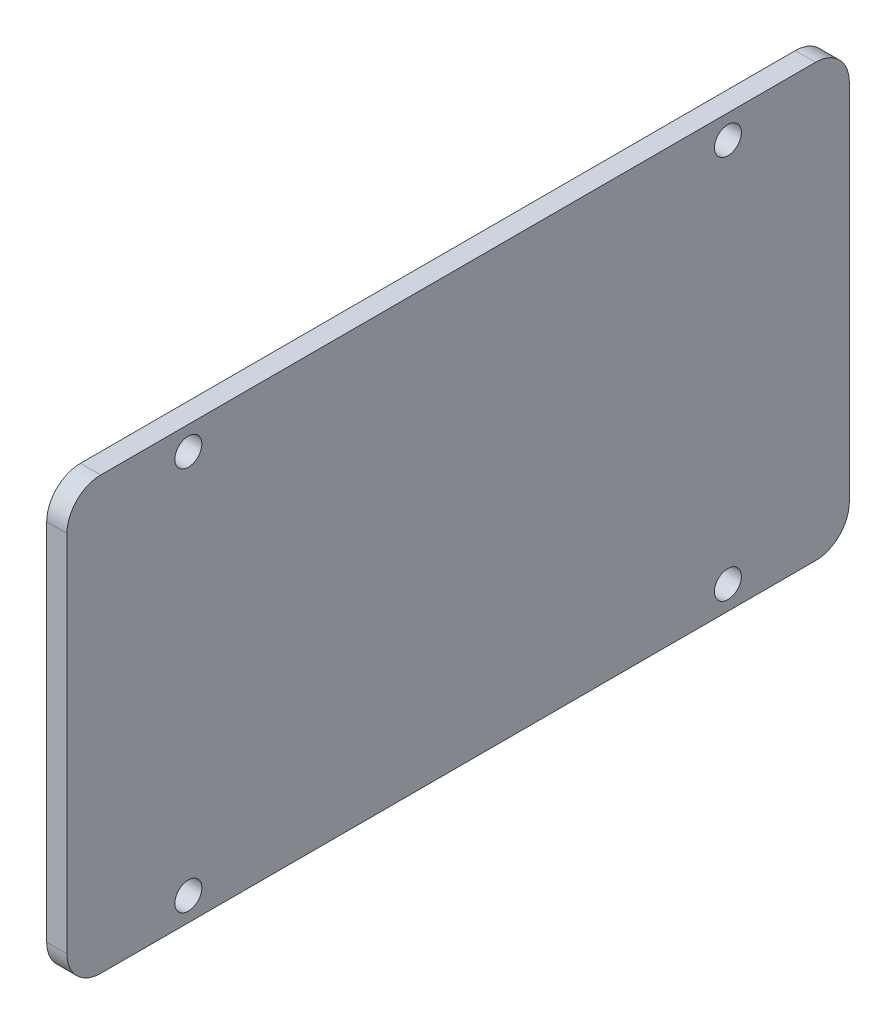
SolidWorks part; units mm, degrees
material "3003 Alloy"
ref_plane "Front Plane" through (0, 0, 0) normal (0, 0, 1) x (1, 0, 0)
ref_plane "Top Plane" through (0, 0, 0) normal (0, 1, 0) x (1, 0, 0)
ref_plane "Right Plane" through (0, 0, 0) normal (1, 0, 0) x (0, 0, -1)
sketch "Sketch1" plane through (0, 0, 0) normal (0, 0, 1) x (1, 0, 0)
  line L0 (0, 0) -> (0, 64)
  dimension "D1" = 64
sheet metal parameters "Sheet-Metal1" thickness 3 parameters "D1"=3
base flange "Base-Flange1" sketch "Sketch1" end condition blind depth 116 reverse direction no thickness 3 reverse thickness direction no bend radius 3
sketch "Sketch3" plane through (0, 0, 0) normal (-1, 0, 0) x (0, 0, 1)
  line L0 (18, 60.5) -> (98, 60.5) construction
  line L1 (58, 64) -> (58, 60.5) construction
  line L2 (116, 64) -> (0, 64) construction
  line L3 (0, 32) -> (116, 32) construction
  line L4 (0, 0) -> (0, 64) construction
  line L5 (116, 0) -> (116, 64) construction
  line L6 (18, 3.5) -> (98, 3.5) construction
  circle A0 centre (18, 60.5) radius 2
  circle A1 centre (98, 60.5) radius 2
  circle A2 centre (98, 3.5) radius 2
  circle A3 centre (18, 3.5) radius 2
  dimension "D3" = 4
  dimension "D1" = 80
  dimension "D2" = 57
extrude "Cut-Extrude1" cut sketch "Sketch3" against normal blind 10 normal cut yes
fillet "Fillet1" radius 5 4 edges at (1.5, 0, 116) (1.5, 0, 0) (1.5, 64, 116) (1.5, 64, 0)
flat pattern "Flat-Pattern1" [suppressed]
sketch "Bend-Lines1" plane through (0, 0, 0) normal (0, 1, 0) x (-1, 0, 0)
